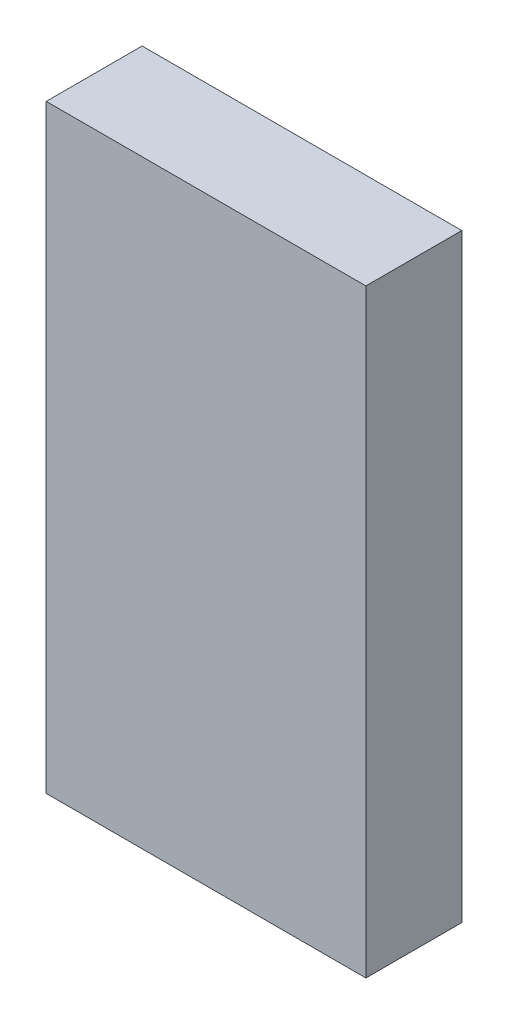
SolidWorks part; units mm, degrees
ref_plane "Front Plane" through (0, 0, 0) normal (0, 0, 1) x (1, 0, 0)
ref_plane "Top Plane" through (0, 0, 0) normal (0, 1, 0) x (1, 0, 0)
ref_plane "Right Plane" through (0, 0, 0) normal (1, 0, 0) x (0, 0, -1)
sketch "Sketch1" plane through (0, 0, 0) normal (0, 1, 0) x (1, 0, 0)
  line L1 (-20, 6) -> (20, 6)
  line L2 (-20, 6) -> (-20, -6)
  line L3 (-20, -6) -> (20, -6)
  line L4 (20, 6) -> (20, -6)
  line L5 (-20, 6) -> (20, -6) construction
  line L6 (-20, -6) -> (20, 6) construction
  point P0 (0, 0)
  dimension "D1" = 12
  dimension "D2" = 40
extrude "Boss-Extrude1" add sketch "Sketch1" along normal mid plane 75
